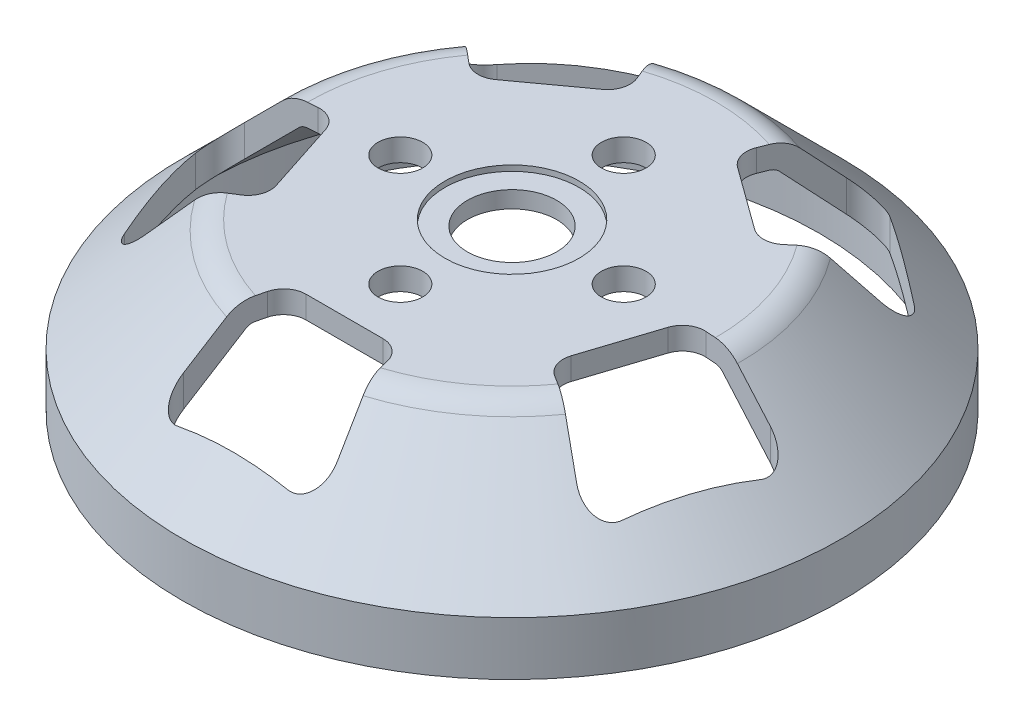
SolidWorks part; units mm, degrees
ref_plane "Front Plane" through (0, 0, 0) normal (0, 0, 1) x (1, 0, 0)
ref_plane "Top Plane" through (0, 0, 0) normal (0, 1, 0) x (1, 0, 0)
ref_plane "Right Plane" through (0, 0, 0) normal (1, 0, 0) x (0, 0, -1)
sketch "Sketch1" plane through (0, 0, 0) normal (0, 1, 0) x (1, 0, 0)
  circle A0 centre (0, 0) radius 29.5
  dimension "D1" = 59
extrude "Boss-Extrude1" add sketch "Sketch1" along normal blind 4.8
sketch "Sketch2" plane through (0, 4.8, 0) normal (0, 1, 0) x (1, 0, 0)
  circle A0 centre (0, 0) radius 29.5 construction
  circle A1 centre (0, 0) radius 29.5
ref_plane "Plane1" through (0, 14.8, 0) normal (0, 1, 0) x (1, 0, 0)
sketch "Sketch3" plane through (0, 14.8, 0) normal (0, 1, 0) x (1, 0, 0)
  circle A0 centre (0, 0) radius 19.5
  dimension "D1" = 39
loft "Loft1" add profiles "Sketch2", "Sketch3" connector at (0, 4.8, 29.5) connector at (0, 14.8, 19.5)
fillet "Fillet1" radius 3 1 edges at (0, 14.8, 19.5) type face fillet first side face at (0, 14.8, 19.5) second side face at (0, 4.8, 29.5)
sketch "Sketch4" plane through (0, 14.8, 0) normal (0, 1, 0) x (1, 0, 0)
  line L0 (3.4384, -15) -> (-3.4384, -15)
  line L1 (0, -15) -> (0, -25) construction
  line L2 (0, -25) -> (-4.9384, -25)
  line L3 (0, -25) -> (4.9384, -25)
  line L4 (6.8787, -22.5149) -> (5.3787, -16.5149)
  line L5 (-6.8787, -22.5149) -> (-5.3787, -16.5149)
  line L6 (-23.7764, -7.7254) -> (-22.2503, -12.4222)
  line L7 (-23.7764, -7.7254) -> (-25.3025, -3.0287)
  line L8 (-23.5386, -0.4154) -> (-17.3688, 0.0121)
  line L9 (-13.2033, -7.9054) -> (-15.3284, -1.3651)
  line L10 (-19.2873, -13.4996) -> (-14.0445, -10.2189)
  line L11 (-14.6946, 20.2254) -> (-18.6899, 17.3227)
  line L12 (-14.6946, 20.2254) -> (-10.6993, 23.1282)
  line L13 (-7.6689, 22.2582) -> (-5.3557, 16.5224)
  line L14 (-11.5985, 10.1142) -> (-6.035, 14.1563)
  line L15 (-18.799, 14.1717) -> (-14.0587, 10.1993)
  line L16 (14.6946, 20.2254) -> (10.6993, 23.1282)
  line L17 (14.6946, 20.2254) -> (18.6899, 17.3227)
  line L18 (18.799, 14.1717) -> (14.0587, 10.1993)
  line L19 (6.035, 14.1563) -> (11.5985, 10.1142)
  line L20 (7.6689, 22.2582) -> (5.3557, 16.5224)
  line L21 (23.7764, -7.7254) -> (25.3025, -3.0287)
  line L22 (23.7764, -7.7254) -> (22.2503, -12.4222)
  line L23 (19.2873, -13.4996) -> (14.0445, -10.2189)
  line L24 (15.3284, -1.3651) -> (13.2033, -7.9054)
  line L25 (23.5386, -0.4154) -> (17.3688, 0.0121)
  circle A0 centre (0, 0) radius 20
  arc A1 (-5.3787, -16.5149) -> (-3.4384, -15) centre (-3.4384, -17) cw
  arc A2 (3.4384, -15) -> (5.3787, -16.5149) centre (3.4384, -17) cw
  arc A3 (-6.8787, -22.5149) -> (-4.9384, -25) centre (-4.9384, -23) ccw
  arc A4 (6.8787, -22.5149) -> (4.9384, -25) centre (4.9384, -23) cw
  arc A5 (-23.5386, -0.4154) -> (-25.3025, -3.0287) centre (-23.4004, -2.4106) ccw
  arc A6 (-17.3688, 0.0121) -> (-15.3284, -1.3651) centre (-17.2305, -1.9831) cw
  arc A7 (-13.2033, -7.9054) -> (-14.0445, -10.2189) centre (-15.1054, -8.5234) cw
  arc A8 (-19.2873, -13.4996) -> (-22.2503, -12.4222) centre (-20.3482, -11.8041) cw
  arc A9 (-7.6689, 22.2582) -> (-10.6993, 23.1282) centre (-9.5238, 21.5101) ccw
  arc A10 (-5.3557, 16.5224) -> (-6.035, 14.1563) centre (-7.2106, 15.7744) cw
  arc A11 (-11.5985, 10.1142) -> (-14.0587, 10.1993) centre (-12.7741, 11.7322) cw
  arc A12 (-18.799, 14.1717) -> (-18.6899, 17.3227) centre (-17.5143, 15.7046) cw
  arc A13 (18.799, 14.1717) -> (18.6899, 17.3227) centre (17.5143, 15.7046) ccw
  arc A14 (14.0587, 10.1993) -> (11.5985, 10.1142) centre (12.7741, 11.7322) cw
  arc A15 (6.035, 14.1563) -> (5.3557, 16.5224) centre (7.2106, 15.7744) cw
  arc A16 (7.6689, 22.2582) -> (10.6993, 23.1282) centre (9.5238, 21.5101) cw
  arc A17 (19.2873, -13.4996) -> (22.2503, -12.4222) centre (20.3482, -11.8041) ccw
  arc A18 (14.0445, -10.2189) -> (13.2033, -7.9054) centre (15.1054, -8.5234) cw
  arc A19 (15.3284, -1.3651) -> (17.3688, 0.0121) centre (17.2305, -1.9831) cw
  arc A20 (23.5386, -0.4154) -> (25.3025, -3.0287) centre (23.4004, -2.4106) cw
  point P11 (-5, -15)
  point P14 (5, -15)
  point P17 (-7.5, -25)
  point P20 (7.5, -25)
  point P76 (0, 0)
  dimension "D1" = 40
  dimension "D6" = 7.5
  dimension "D8" = 2
  dimension "D2" = 10
  dimension "D3" = 5
  dimension "D4" = 15
  dimension "D5" = 10
  dimension "D7" = 7.5
  dimension "D9" = 5
shell "Shell1" thickness 2 removed face at (0, 0, 29.5)
extrude "Cut-Extrude2" cut sketch "Sketch4" against normal blind 10 contours A20 L25 A0 L23 A17 L22 L21 | A19 L24 A18 L23 A0 L25 | A15 L19 A14 L18 A0 L20 | A16 L20 A0 L18 A13 L17 L16 | A11 L14 A10 L13 A0 L15 | A12 L15 A0 L13 A9 L12 L11 | A8 L10 A0 L8 A5 L7 L6 | A7 L9 A6 L8 A0 L10 | L1 A0 L5 A3 L2 | A0 L1 L3 A4 L4 | L0 L1 A0 L4 A2 | L1 L0 A1 L5 A0 region at (2.6536, 14.8, 17.4727) region at (-2.6536, 14.8, 17.4727) region at (3.37, 14.8, 22.3369) region at (-3.37, 14.8, 22.3369) region at (21.2437, 14.8, 6.9025) region at (16.6175, 14.8, 5.3994) region at (-16.6175, 14.8, 5.3994) region at (-21.2437, 14.8, 6.9025) region at (-10.2702, 14.8, -14.1357) region at (-13.1293, 14.8, -18.071) region at (13.1293, 14.8, -18.071) region at (10.2702, 14.8, -14.1357)
sketch "Sketch5" plane through (0, 14.8, 0) normal (0, 1, 0) x (1, 0, 0)
  circle A0 centre (0, 0) radius 4
  circle A1 centre (0, 0) radius 6
  dimension "D1" = 12
  dimension "D2" = 8
extrude "Cut-Extrude3" cut sketch "Sketch5" against normal blind 10 contours A0 region at (0, 14.8, 0)
extrude "Cut-Extrude4" cut sketch "Sketch5<3>" against normal blind 0.5
sketch "Sketch5<3>" plane through (0, 14.8, 0) normal (0, 1, 0) x (1, 0, 0) same geometry as "Sketch5"
sketch "Sketch6" plane through (0, 14.8, 0) normal (0, 1, 0) x (1, 0, 0)
  circle A0 centre (0, 0) radius 10 construction
  circle A1 centre (0, 10) radius 2
  circle A2 centre (10, 0) radius 2
  circle A3 centre (0, -10) radius 2
  circle A4 centre (-10, 0) radius 2
  point P14 (0, 0)
  dimension "D1" = 20
  dimension "D2" = 4
  dimension "D3" = 4
extrude "Cut-Extrude5" cut sketch "Sketch6" against normal blind 10.5
